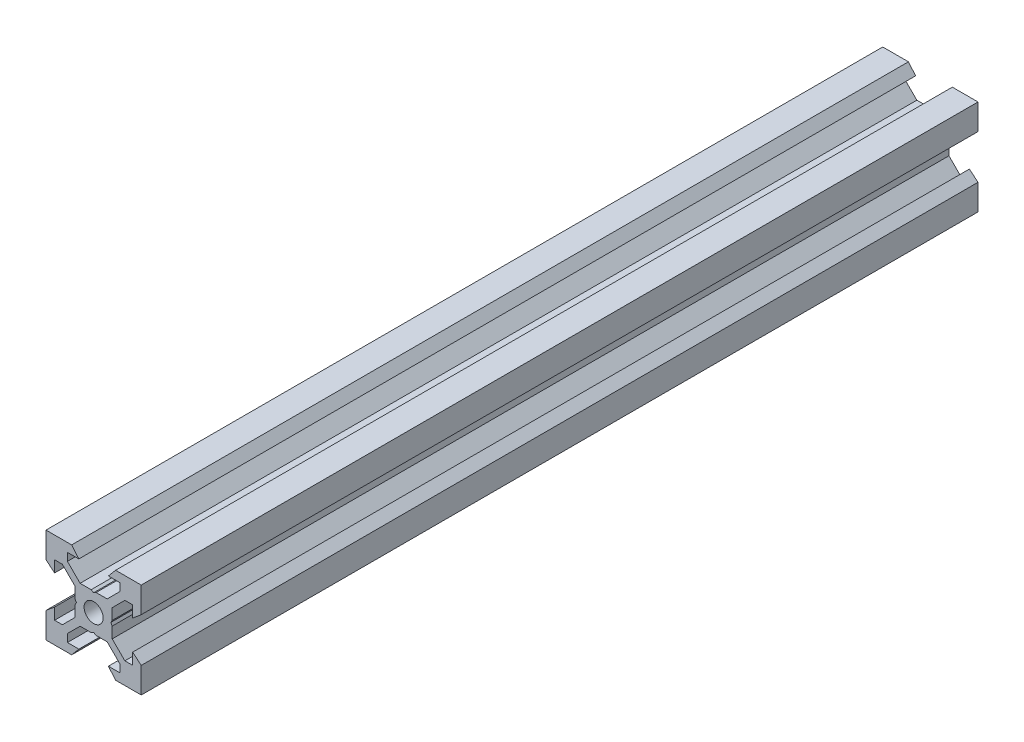
SolidWorks part; units mm, degrees
ref_plane "Front Plane" through (0, 0, 0) normal (0, 0, 1) x (1, 0, 0)
ref_plane "Top Plane" through (0, 0, 0) normal (0, 1, 0) x (1, 0, 0)
ref_plane "Right Plane" through (0, 0, 0) normal (1, 0, 0) x (0, 0, -1)
sketch "Sketch1" plane through (0, 0, 0) normal (0, 0, 1) x (1, 0, 0)
  line L0 (10, 10) -> (4.6104, 10) construction
  line L1 (10, 10) -> (10, 4.6104) construction
  line L2 (10, -10) -> (10, -4.6104) construction
  line L3 (10, -10) -> (4.6104, -10) construction
  line L4 (10, 10) -> (10, 4.6104)
  line L5 (6.5607, 5.5) -> (8.2, 5.5)
  line L6 (5.5, 8.2) -> (5.5, 6.5607)
  line L7 (10, 10) -> (4.6104, 10)
  line L8 (10, 10) -> (10, 4.6104)
  line L9 (6.5607, 5.5) -> (3.9, 2.8393)
  line L10 (5.5, 6.5607) -> (2.8393, 3.9)
  line L11 (10, 4.6104) -> (8.2, 3.1)
  line L12 (4.6104, 10) -> (3.1, 8.2)
  line L13 (8.2, 3.1) -> (8.2, 5.5)
  line L14 (3.1, 8.2) -> (5.5, 8.2)
  line L15 (-6.5607, 5.5) -> (-8.2, 5.5)
  line L16 (6.5607, -5.5) -> (8.2, -5.5)
  line L17 (3.1, -8.2) -> (5.5, -8.2)
  line L18 (8.2, -3.1) -> (8.2, -5.5)
  line L19 (4.6104, -10) -> (3.1, -8.2)
  line L20 (10, -4.6104) -> (8.2, -3.1)
  line L21 (0.5196, -3.9) -> (0, -3.6)
  line L22 (0.5196, 3.9) -> (0, 3.6)
  line L23 (3.6, 0) -> (3.9, -0.5196)
  line L24 (3.9, 0.5196) -> (3.6, 0)
  line L25 (3.9, 0.5196) -> (3.9, 2.8393)
  line L26 (2.8393, 3.9) -> (0.5196, 3.9)
  line L27 (3.9, -2.8393) -> (3.9, -0.5196)
  line L28 (2.8393, -3.9) -> (0.5196, -3.9)
  line L29 (5.5, -6.5607) -> (2.8393, -3.9)
  line L30 (6.5607, -5.5) -> (3.9, -2.8393)
  line L31 (10, -10) -> (10, -4.6104)
  line L32 (10, -10) -> (4.6104, -10)
  line L33 (5.5, -8.2) -> (5.5, -6.5607)
  line L34 (-6.5607, -5.5) -> (-8.2, -5.5)
  line L35 (10, -10) -> (10, -4.6104)
  line L36 (0, 0) -> (0, 8.2) construction
  line L37 (-10, -10) -> (-4.6104, -10) construction
  line L38 (-10, -10) -> (-10, -4.6104) construction
  line L39 (-10, 10) -> (-10, 4.6104) construction
  line L40 (-10, 10) -> (-4.6104, 10) construction
  line L41 (-10, -10) -> (-10, -4.6104)
  line L43 (-5.5, -8.2) -> (-5.5, -6.5607)
  line L44 (-10, -10) -> (-4.6104, -10)
  line L45 (-10, -10) -> (-10, -4.6104)
  line L46 (-6.5607, -5.5) -> (-3.9, -2.8393)
  line L47 (-5.5, -6.5607) -> (-2.8393, -3.9)
  line L48 (-2.8393, -3.9) -> (-0.5196, -3.9)
  line L49 (-3.9, -2.8393) -> (-3.9, -0.5196)
  line L50 (-2.8393, 3.9) -> (-0.5196, 3.9)
  line L51 (-3.9, 0.5196) -> (-3.9, 2.8393)
  line L52 (-3.9, 0.5196) -> (-3.6, 0)
  line L53 (-3.6, 0) -> (-3.9, -0.5196)
  line L54 (-0.5196, 3.9) -> (0, 3.6)
  line L55 (-0.5196, -3.9) -> (0, -3.6)
  line L56 (-10, -4.6104) -> (-8.2, -3.1)
  line L57 (-4.6104, -10) -> (-3.1, -8.2)
  line L58 (-8.2, -3.1) -> (-8.2, -5.5)
  line L59 (-3.1, -8.2) -> (-5.5, -8.2)
  line L60 (-10, -10) -> (10, -10) construction
  line L61 (-10, -10) -> (-10, 10) construction
  line L62 (-3.1, 8.2) -> (-5.5, 8.2)
  line L63 (-8.2, 3.1) -> (-8.2, 5.5)
  line L64 (-4.6104, 10) -> (-3.1, 8.2)
  line L65 (-10, 4.6104) -> (-8.2, 3.1)
  line L66 (-5.5, 6.5607) -> (-2.8393, 3.9)
  line L67 (-6.5607, 5.5) -> (-3.9, 2.8393)
  line L68 (-10, 10) -> (-10, 4.6104)
  line L69 (-10, 10) -> (-4.6104, 10)
  line L70 (-5.5, 8.2) -> (-5.5, 6.5607)
  line L71 (-10, 10) -> (10, 10) construction
  line L72 (-10, 10) -> (-10, 4.6104)
  line L73 (10, -10) -> (10, 10) construction
  line L74 (-10, -10) -> (10, 10) construction
  line L75 (-10, 10) -> (10, -10) construction
  circle A0 centre (0, 0) radius 2
  dimension "D7" = 4
  dimension "D1" = 20
  dimension "D2" = 5.3896
  dimension "D3" = 4.5
  dimension "D4" = 50
  dimension "D5" = 1.8
  dimension "D6" = 1.5104
  dimension "D8" = 5.5
  dimension "D9" = 120
  dimension "D10" = 0.3
  dimension "D11" = 2.3197
  dimension "D12" = 7.8
  dimension "D13" = 7.8
  dimension "D14" = 1.5
  dimension "D15" = 2.6607
extrude "Boss-Extrude1" add sketch "Sketch1" along normal mid plane 175.71 contours L70 L62 L64 L69 L68 L65 L63 L15 L67 L51 L52 L53 L49 L46 L34 L58 L56 L41 L44 L57 L59 L43 L47 L48 L55 L21 L28 L29 L33 L17 L19 L32 L31 L20 L18 L16 L30 L27 L23 L24 L25 L9 L5 L13 L11 L4 L7 L12 L14 L6 L10 region at (9.7172, 7.3052, 0)
